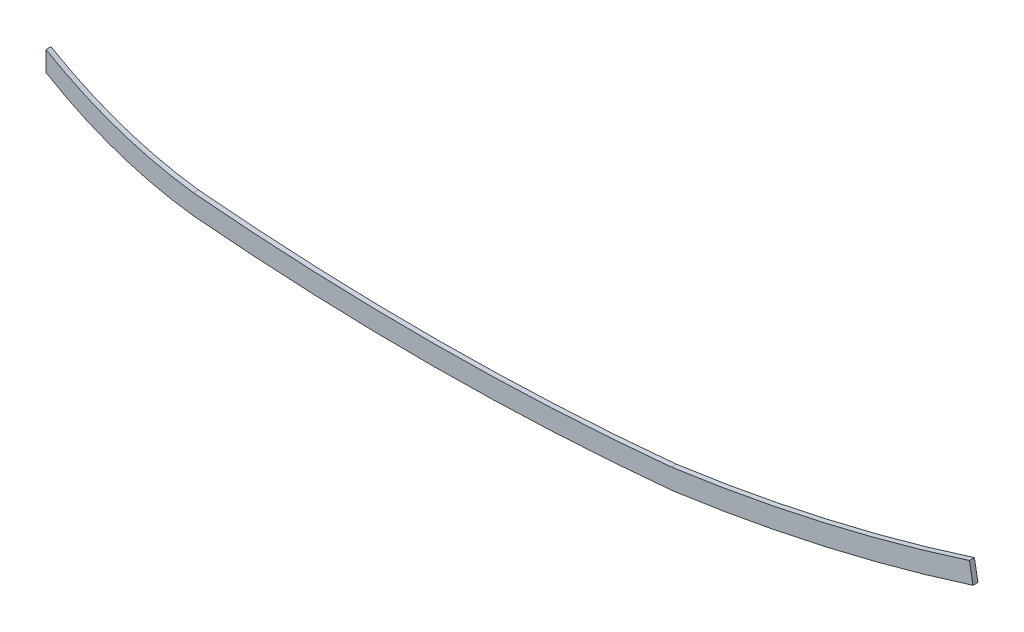
SolidWorks part; units mm, degrees
material "Balsa"
ref_plane "Front Plane" through (0, 0, 0) normal (0, 0, 1) x (1, 0, 0)
ref_plane "Top Plane" through (0, 0, 0) normal (0, 1, 0) x (1, 0, 0)
ref_plane "Right Plane" through (0, 0, 0) normal (1, 0, 0) x (0, 0, -1)
sketch "Sketch2" plane through (0, 0, 0) normal (0, 0, 1) x (1, 0, 0)
  line L0 (0, -93.726) -> (0, -81.026)
  line L2 (93.98, 0) -> (93.98, -379.755) construction
  line L3 (398.3737, -110.9898) -> (402.5381, -142.3403) construction
  line L4 (398.3737, -110.9898) -> (366.1948, 131.2634) construction
  line L7 (590.8643, -81.3536) -> (588.579, -68.7797)
  line L8 (0, 0) -> (672.417, 0) construction
  arc A0 (0, -93.726) -> (93.98, -125.8052) centre (121.8415, 109.5207) ccw
  arc A1 (93.98, -125.8052) -> (400.2036, -124.7658) centre (241.5116, 1518.5899) ccw
  arc A2 (400.2036, -124.7658) -> (590.8643, -81.3536) centre (242.7057, 1007.3312) ccw
  arc A3 (95.6211, -113.2301) -> (398.7207, -112.1786) centre (241.5116, 1518.5899) ccw construction
  arc A4 (93.9818, -113.0827) -> (398.7207, -112.1786) centre (241.5116, 1518.5899) ccw
  arc A5 (398.7207, -112.1786) -> (588.579, -68.7797) centre (242.7057, 1007.3312) ccw
  arc A6 (94.4927, -125.8512) -> (400.2036, -124.7658) centre (241.5116, 1518.5899) ccw construction
  arc A7 (398.7207, -112.1786) -> (587.0046, -69.2844) centre (242.7057, 1007.3312) ccw construction
  arc A9 (0, -81.026) -> (93.9818, -113.0827) centre (124.7234, 130.8365) ccw
  spline S0 degree 3 poles (3.7499, -94.8626) (10.597, -99.2271) (17.6385, -103.1401) (32.0968, -110.0953) (39.5136, -113.1375) (50.922, -117.0433) (54.7721, -118.2354) (60.6197, -119.8556) (62.5829, -120.3681) (66.5243, -121.3341) (68.5001, -121.787) (78.4043, -123.9021) (86.408, -125.1172) (94.4926, -125.8525) knots 0 0 0 0 0.25 0.25 0.5 0.5 0.625 0.625 0.6875 0.6875 0.75 0.75 1 1 1 1 construction
  spline S1 degree 3 poles (94.4926, -125.8525) (120.9278, -128.4258) (173.8258, -132.179) (226.7788, -133.168) (266.5142, -132.8729) (279.7628, -132.6016) (299.6408, -131.9345) (306.2677, -131.6688) (319.5231, -131.0505) (326.1536, -130.6977) (359.2877, -128.7173) (385.6949, -126.4433) (412.003, -123.4859) knots 0 0 0 0 0.25 0.5 0.5 0.625 0.625 0.6875 0.6875 0.75 0.75 1 1 1 1 construction
  point P3 (0, 0)
  dimension "D3" = 236.9696
  dimension "D4" = 1651
  dimension "D5" = 1143
  dimension "D6" = 79.699
  dimension "D7" = 1638.3286
  dimension "D8" = 245.8488
  dimension "D1" = 12.7
  dimension "D2" = 93.726
  dimension "D9" = 93.9818
extrude "Boss-Extrude1" add sketch "Sketch2" along normal blind 3.175
